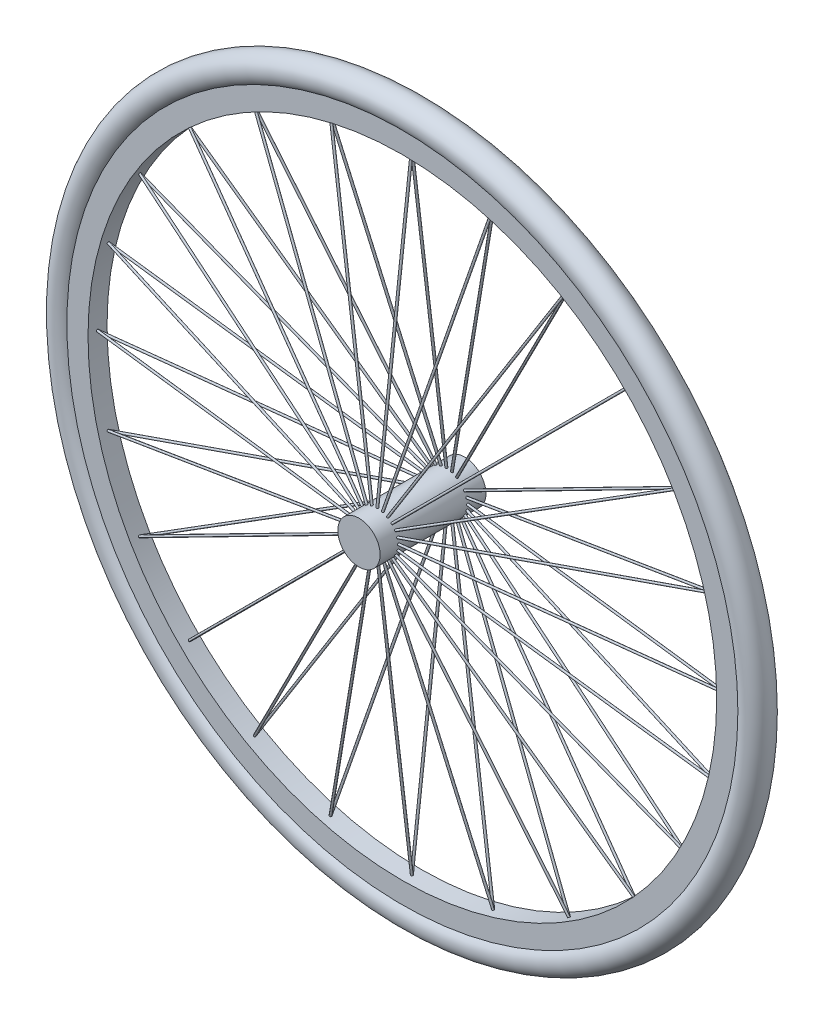
SolidWorks part; units mm, degrees
material "车轮"
ref_plane "前视基准面" through (0, 0, 0) normal (0, 0, 1) x (1, 0, 0)
ref_plane "上视基准面" through (0, 0, 0) normal (0, 1, 0) x (1, 0, 0)
ref_plane "右视基准面" through (0, 0, 0) normal (1, 0, 0) x (0, 0, -1)
other "Configuration Table"
sketch "草图1" plane through (0, 0, 0) normal (0, 0, 1) x (1, 0, 0)
  circle A0 centre (0, 0) radius 20
  dimension "D1" = 40
extrude "凸台-拉伸1" add sketch "草图1" along normal mid plane 100
sketch "草图2" plane through (0, 0, 0) normal (0, 1, 0) x (1, 0, 0)
  line L1 (297.1439, 9) -> (317.1439, 9)
  line L2 (297.1439, 9) -> (297.1439, -9)
  line L3 (297.1439, -9) -> (317.1439, -9)
  line L5 (297.1439, 9) -> (317.1439, -9) construction
  line L6 (297.1439, -9) -> (317.1439, 9) construction
  arc A0 (317.1439, -9) -> (317.1439, 9) centre (326.8, 0) ccw
  point P0 (307.1439, 0)
  dimension "D1" = 26.4
  dimension "D4" = 326.8
  dimension "D2" = 18
  dimension "D3" = 20
sketch "草图3" plane through (0, 0, 0) normal (0, 1, 0) x (1, 0, 0)
  line L0 (0, -50) -> (0, 50)
  line L1 (-20, -50) -> (20, -50) construction
  line L2 (20, 50) -> (-20, 50) construction
revolve "旋转1" add sketch "草图2" angle 360 about L0
sketch "草图5" plane through (0, 0, 0) normal (0, 1, 0) x (1, 0, 0)
  line L0 (297.1439, 9) -> (-297.1439, 9) construction
  line L3 (297.1439, 9) -> (-297.1439, 9)
  line L4 (0, -35) -> (297.1439, 0)
  line L5 (297.1439, -9) -> (297.1439, 9) construction
  arc A0 (326.8, -13.2) -> (326.8, 13.2) centre (326.8, 0) ccw construction
  arc A1 (326.8, -13.2) -> (326.8, 13.2) centre (326.8, 0) ccw
  dimension "D2" = 35
ref_plane "基准面1" through (0, 0, 35) normal (0.9931, 0, -0.117) x (-0.117, 0, -0.9931)
sketch "草图6" plane through (0, 0, 35) normal (0.9931, 0, -0.117) x (-0.117, 0, -0.9931)
  circle A0 centre (0, 0) radius 1
  dimension "D1" = 2
extrude "凸台-拉伸2" add sketch "草图6" along normal up to surface (299.3159 mm away) up to face at (297.1439, 0, 9)
pattern_circular "阵列(圆周)1" count 24 over 360 about axis through (0, 0, 50) along (0, 0, 1) of "凸台-拉伸2"
mirror "镜向1" about plane through (0, 0, 0) normal (0, 0, 1) of "阵列(圆周)1"
